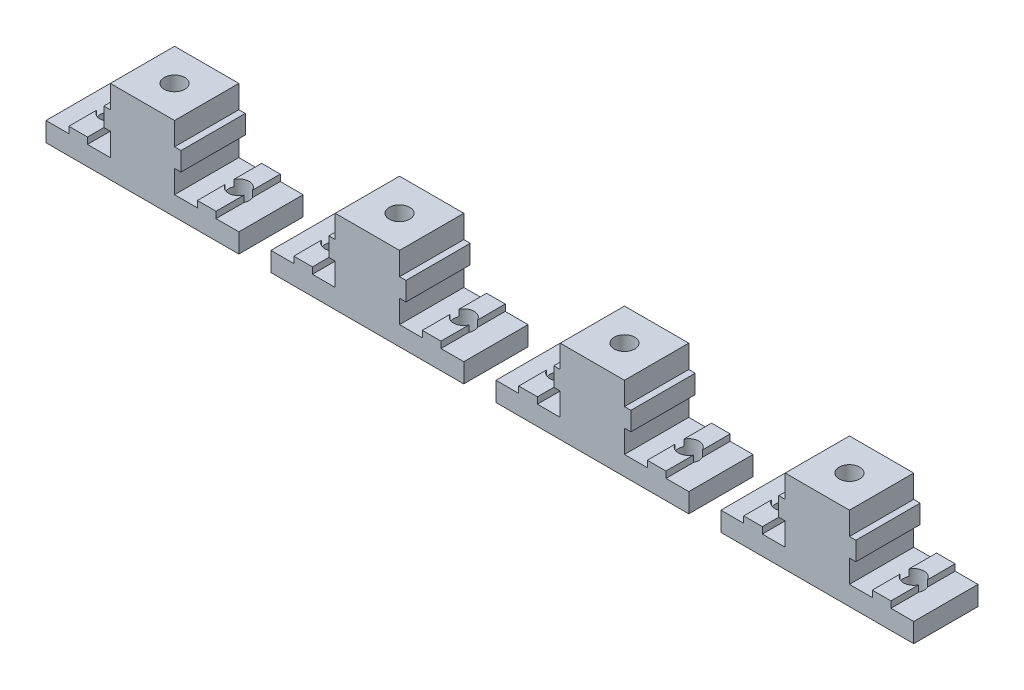
SolidWorks part; units mm, degrees
ref_plane "Front Plane" through (0, 0, 0) normal (0, 0, 1) x (1, 0, 0)
ref_plane "Top Plane" through (0, 0, 0) normal (0, 1, 0) x (1, 0, 0)
ref_plane "Right Plane" through (0, 0, 0) normal (1, 0, 0) x (0, 0, -1)
sketch "Esquisse1" plane through (0, 0, 0) normal (0, 0, 1) x (1, 0, 0)
  line L0 (-15, 0) -> (-15, 3)
  line L1 (-15, 3) -> (-11.45, 3)
  line L2 (-11.45, 3) -> (-11.45, 4)
  line L3 (-11.45, 4) -> (-8.55, 4)
  line L4 (-8.55, 4) -> (-8.55, 3)
  line L5 (-8.55, 3) -> (-5, 3)
  line L6 (-5, 3) -> (-5, 6.55)
  line L7 (0, 0) -> (-15, 0)
  line L8 (-5, 6.55) -> (-6, 6.55)
  line L9 (-6, 6.55) -> (-6, 9.45)
  line L10 (-6, 9.45) -> (-5, 9.45)
  line L11 (-5, 9.45) -> (-5, 13)
  line L12 (-5, 13) -> (0, 13)
  line L13 (0, 13) -> (0, 0)
  point P8 (6.5161, 3)
  point P11 (0, 0)
  point P18 (5.5294, 0)
  point P19 (9.6212, 0)
  point P20 (5.7615, 6.163)
  point P21 (10.9562, 0)
  point P22 (5.3262, 6.076)
  point P23 (6.429, 8.2235)
  point P24 (0, 0)
  dimension "D1" = 15
  dimension "D2" = 3
  dimension "D3" = 1
  dimension "D4" = 2.9
  dimension "D5" = 3.55
  dimension "D6" = 5
  dimension "D7" = 10
  dimension "D8" = 2.9
  dimension "D9" = 3.55
extrude "Main" add sketch "Esquisse1" along normal blind 10
sketch "Esquisse2" plane through (0, 4, 0) normal (0, 1, 0) x (1, 0, 0)
  line L2 (-11.45, -10) -> (-15, -10) construction
  line L4 (-8.55, 0) -> (-11.45, 0) construction
  circle A1 centre (-10, -5) radius 1.6
  point P4 (0, 0)
  point P5 (0, -2.3892)
  point P6 (0, -16.6698)
  point P7 (0, 0)
  point P8 (-10.0257, -15)
  point P9 (-10.0257, -5)
  point P10 (0, -2.5276)
  point P11 (0, -16.7528)
  point P12 (-10, 0)
  point P16 (0, 0)
  dimension "D2" = 5
  dimension "D3" = 3.2
  dimension "D1" = 5
extrude "TopHole" cut sketch "Esquisse2" against normal through all
ref_axis "Axe1" through (-5.5, 0, 0) along (1, 0, 0)
mirror "Symétrie1" about plane through (0, 0, 0) normal (1, 0, 0) of "Main", "TopHole"
sketch "Esquisse3" plane through (0, 13, 0) normal (0, 1, 0) x (1, 0, 0)
  line L0 (0, -2.2) -> (0, 2.2) construction
  line L2 (5, -10) -> (-5, -10) construction
  circle A1 centre (0, -5) radius 1.6
  point P7 (0, 0)
  point P10 (0, -4.6892)
  point P11 (0, -14.9499)
  point P12 (0, 0)
  dimension "D1" = 3.2
  dimension "D2" = 5
extrude "Enlèv. mat.-Extru.2" cut sketch "Esquisse3" against normal through all
ref_axis "Axe2" through (16.5, 0, 0) along (-1, 0, 0)
pattern_linear "Répétition linéaire3" count 4 spacing 35 along (1, 0, 0) of bodies 108
